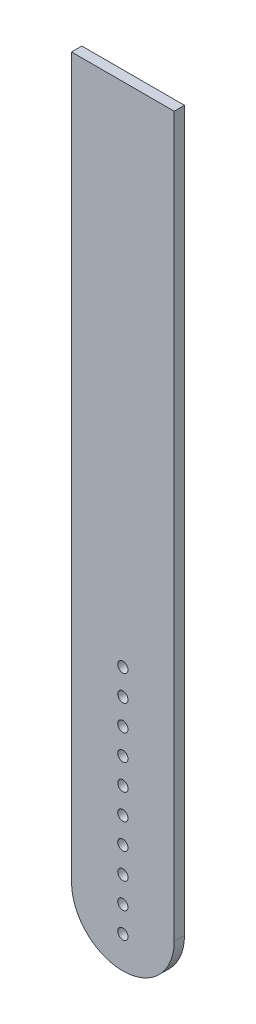
SolidWorks part; units mm, degrees
ref_plane "Front Plane" through (0, 0, 0) normal (0, 0, 1) x (1, 0, 0)
ref_plane "Top Plane" through (0, 0, 0) normal (0, 1, 0) x (1, 0, 0)
ref_plane "Right Plane" through (0, 0, 0) normal (1, 0, 0) x (0, 0, -1)
sketch "Sketch1" plane through (0, 0, 0) normal (0, 1, 0) x (1, 0, 0)
  line L1 (-20, 2) -> (20, 2)
  line L2 (-20, 2) -> (-20, -2)
  line L3 (-20, -2) -> (20, -2)
  line L4 (20, 2) -> (20, -2)
  line L5 (-20, 2) -> (20, -2) construction
  line L6 (-20, -2) -> (20, 2) construction
  point P0 (0, 0)
extrude "Boss-Extrude1" add sketch "Sketch1" along normal blind 300
fillet "Fillet1" radius 20 2 edges at (-20, 0, 0) (20, 0, 0)
sketch "Sketch2" plane through (0, 0, 2) normal (0, 0, 1) x (1, 0, 0)
  circle A0 centre (0, 12.5) radius 2
  dimension "D1" = 12.5
extrude "Cut-Extrude1" cut sketch "Sketch2" against normal through all
pattern_linear "LPattern1" count 10 spacing 10 along (0, 1, 0) of "Cut-Extrude1"
sketch "Sketch6" plane through (0, 0, -2) normal (0, 0, -1) x (-1, 0, 0)
  line L1 (-6.5, 1.0857) -> (-8.5, 1.0857)
  line L2 (-6.5, 1.0857) -> (-6.5, 126.0857)
  line L3 (-6.5, 126.0857) -> (-8.5, 126.0857)
  line L4 (-8.5, 1.0857) -> (-8.5, 126.0857)
  line L5 (-7.5, 126.0857) -> (-7.5, 1.0857) construction
  line L6 (-6.5, 63.5857) -> (-8.5, 63.5857) construction
  line L7 (-20, 300) -> (-20, 20) construction
  arc A0 (-20, 20) -> (0, 0) centre (0, 20) ccw construction
  point P524 (-7.5, 63.5857)
  dimension "D1" = 2
  dimension "D2" = 12.5
  dimension "D3" = 125
extrude "Cut-Extrude3" cut sketch "Sketch6" against normal blind 2 contours L3 L4 L1 L2
fillet "Fillet2" radius 1 2 edges at (8.5, 126.0857, -1) (6.5, 126.0857, -1)
mirror "Mirror1" about plane through (0, 0, 0) normal (1, 0, 0) of "Fillet2", "Cut-Extrude3"
